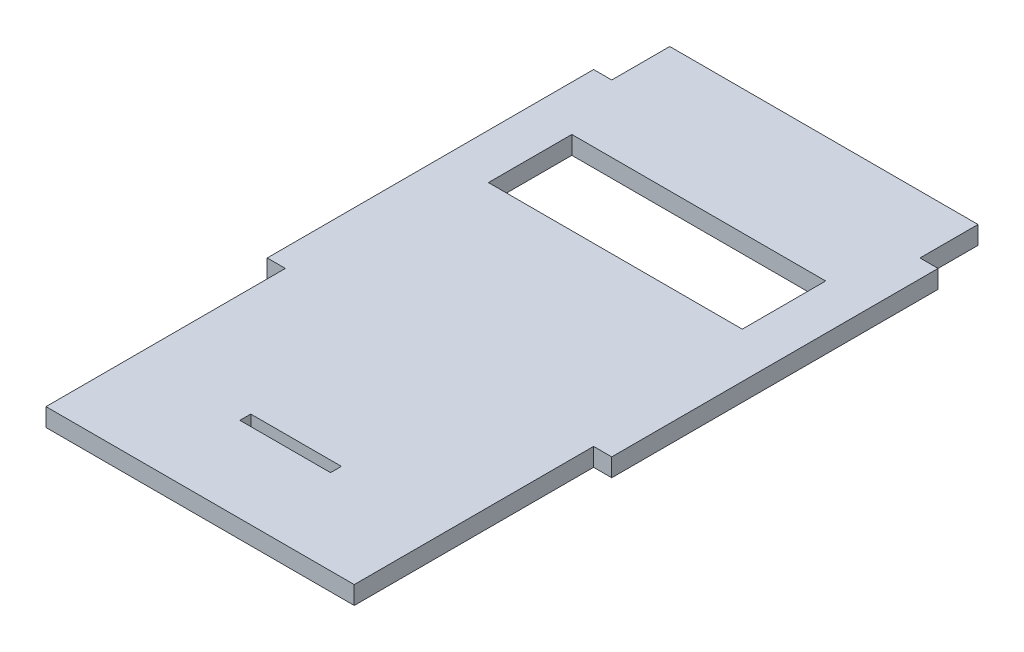
SolidWorks part; units mm, degrees
ref_plane "Alzado" through (0, 0, 0) normal (0, 0, 1) x (1, 0, 0)
ref_plane "Planta" through (0, 0, 0) normal (0, 1, 0) x (1, 0, 0)
ref_plane "Vista lateral" through (0, 0, 0) normal (1, 0, 0) x (0, 0, -1)
sketch "Croquis1" plane through (0, 0, 0) normal (0, 1, 0) x (1, 0, 0)
  line L0 (-42.5, -20) -> (42.5, -20) construction
  line L1 (-42.5, -86) -> (42.5, -86)
  line L2 (-42.5, -86) -> (-42.5, -20)
  line L3 (-42.5, 86) -> (42.5, 86)
  line L4 (42.5, -86) -> (42.5, -20)
  line L5 (-42.5, -86) -> (42.5, 86) construction
  line L6 (-42.5, 86) -> (42.5, -86) construction
  line L7 (-42.5, 70) -> (-42.5, 86)
  line L8 (-42.5, -20) -> (-47.5, -20)
  line L9 (42.5, 70) -> (42.5, 86)
  line L10 (-42.5, 70) -> (-47.5, 70)
  line L11 (-47.5, -20) -> (-47.5, 70)
  line L12 (42.5, 70) -> (47.5, 70)
  line L13 (0, 86) -> (0, -86) construction
  line L14 (42.5, -20) -> (47.5, -20)
  line L15 (47.5, 70) -> (47.5, -20)
  line L17 (-12.5, -62.5396) -> (12.5, -62.5396)
  line L18 (-12.5, -62.5396) -> (-12.5, -59.5396)
  line L19 (-12.5, -59.5396) -> (12.5, -59.5396)
  line L20 (12.5, -62.5396) -> (12.5, -59.5396)
  line L21 (-12.5, -62.5396) -> (12.5, -59.5396) construction
  line L22 (-12.5, -59.5396) -> (12.5, -62.5396) construction
  line L23 (-35, 28.5) -> (35, 28.5)
  line L24 (-35, 28.5) -> (-35, 51.5)
  line L25 (-35, 51.5) -> (35, 51.5)
  line L26 (35, 28.5) -> (35, 51.5)
  line L27 (-35, 28.5) -> (35, 51.5) construction
  line L28 (-35, 51.5) -> (35, 28.5) construction
  point P0 (0, 0)
  point P16 (0, -61.0396)
  point P21 (0, 40)
  dimension "D1" = 172
  dimension "D2" = 85
  dimension "D3" = 16
  dimension "D4" = 90
  dimension "D5" = 5
  dimension "D6" = 5
  dimension "D7" = 25
  dimension "D8" = 3
  dimension "D9" = 70
  dimension "D10" = 23
  dimension "D11" = 40
extrude "Saliente-Extruir1" add sketch "Croquis1" along normal blind 5
